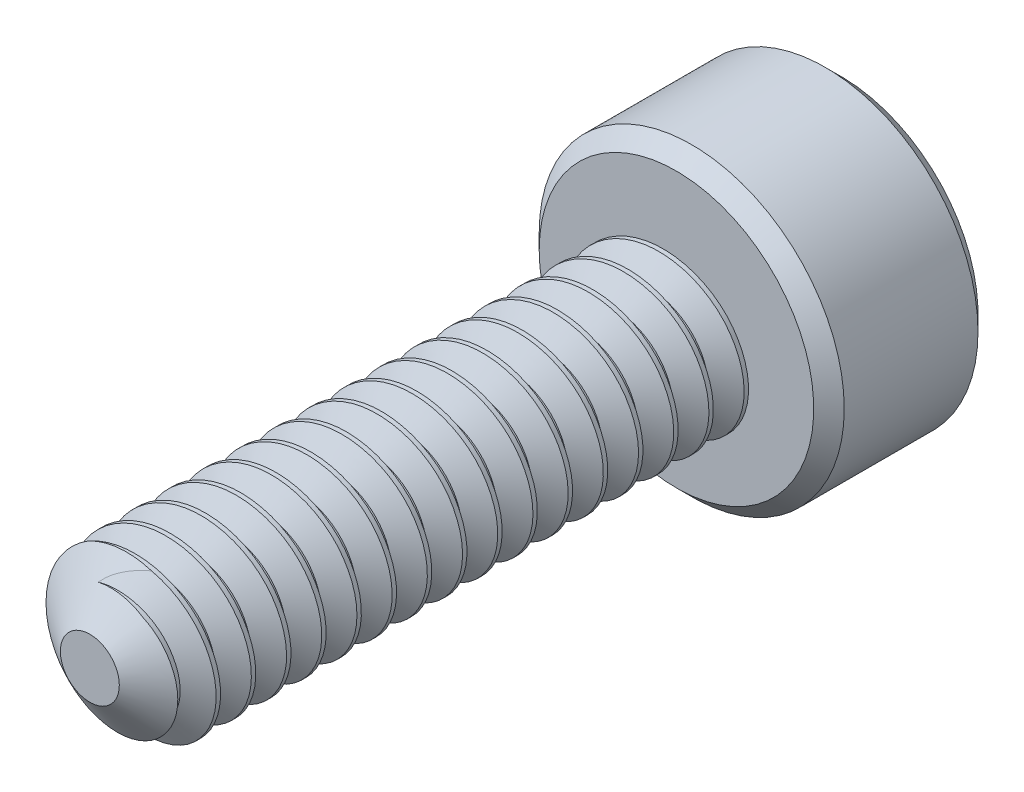
SolidWorks part; units mm, degrees
other "DetailItem1"
ref_plane "Front Plane" through (0, 0, 0) normal (0, 0, 1) x (1, 0, 0)
ref_plane "Top Plane" through (0, 0, 0) normal (0, 1, 0) x (1, 0, 0)
ref_plane "Right Plane" through (0, 0, 0) normal (1, 0, 0) x (0, 0, -1)
sketch "Sketch1" plane through (0, 0, 0) normal (0, 0, 1) x (1, 0, 0)
  circle A0 centre (0, 0) radius 0.7
  dimension "OD" = 1.4
extrude "Extrude1" add sketch "Sketch1" against normal blind 5
sketch "Sketch2" plane through (0, 0, 0) normal (0, 0, 1) x (1, 0, 0)
  circle A0 centre (0, 0) radius 0.7 construction
  circle A1 centre (0, 0) radius 0.7
curve "Helix/Spiral1" pitch 0.3 height 5.3 radius 0.7 centre (0, 0, 0) axis (0, 0, -1) start towards (0, 1, 0) parameters "pitch"=0.3
sketch "Sketch3" plane through (0, 0, 0) normal (1, 0, 0) x (0, 0, -1)
  line L0 (-0.2625, 0.7) -> (-0.15, 0.5051)
  line L1 (-0.15, 0.5051) -> (-0.1125, 0.5051)
  line L2 (-0.1125, 0.5051) -> (0, 0.7)
  line L3 (-0.2625, 0.7) -> (0, 0.7)
  line L4 (-0.1313, 0.7) -> (-0.1313, 0.5051) construction
  line L5 (-0.2063, 0.6026) -> (-0.0563, 0.6026) construction
  line L6 (0, 0.7) -> (0, -0.7) construction
  dimension "D1" = 0.0375
  dimension "D2" = 0.15
  dimension "D3" = 60
sweep "Cut-Sweep1" cut profiles "Sketch3" path "Helix/Spiral1" align with end faces yes
sketch "Sketch4" plane through (0, 0, 0) normal (1, 0, 0) x (0, 0, -1)
  line L0 (0.3143, 0.7) -> (0, 0.2511)
  line L1 (0, 0.2511) -> (0, 0.7)
  line L2 (0.3143, 0.7) -> (0, 0.7)
  line L3 (-0.2625, 0.7) -> (0, 0.7) construction
  line L4 (0, 0) -> (7.0209, 0) construction
  dimension "D1" = 55
  dimension "D2" = 0.254
revolve "Cut-Revolve1" cut sketch "Sketch4" angle 360 about L4
sketch "Sketch6" plane through (0, 0, -5) normal (0, 0, -1) x (-1, 0, 0)
  circle A0 centre (0, 0) radius 1.3
  dimension "head dia" = 2.6
extrude "Extrude2" add sketch "Sketch6" along normal blind 1.4
sketch "Sketch7" plane through (0, 0, -6.4) normal (0, 0, -1) x (-1, 0, 0)
  line L1 (0, 0.7506) -> (-0.65, 0.3753)
  line L2 (-0.65, 0.3753) -> (-0.65, -0.3753)
  line L3 (-0.65, -0.3753) -> (0, -0.7506)
  line L4 (0, -0.7506) -> (0.65, -0.3753)
  line L5 (0.65, -0.3753) -> (0.65, 0.3753)
  line L6 (0.65, 0.3753) -> (0, 0.7506)
  circle A0 centre (0, 0) radius 0.65 construction
  dimension "hex dia" = 1.3
extrude "Cut-Extrude1" cut sketch "Sketch7" against normal blind 0.975
sketch "Sketch8" plane through (0, 0, -6.4) normal (0, 0, -1) x (-1, 0, 0)
  circle A0 centre (0, 0) radius 0.7506
extrude "Cut-Extrude2" cut sketch "Sketch8" against normal through all draft 45
chamfer "Chamfer1" distance 0.13 angle 45 2 edges at (-1.3, 0, -6.4) (-1.3, 0, -5)
sketch "Sketch10" plane through (0, 0, -5) normal (0, 0, 1) x (1, 0, 0)
  circle A1 centre (0, 0) radius 0.7
  circle A2 centre (0, 0) radius 0.7
  dimension "D1" = 0
ref_plane "Plane1" through (0, 0, 0) normal (0, 0, 1) x (1, 0, 0)
extrude "partial thread" [suppressed] add sketch "Sketch10" along normal up to surface (36 mm away) separate body up to plane "Plane1"
chamfer "Chamfer2" [suppressed] distance 0.028 angle 45
combine bodies "Combine1" [suppressed] operation type add bodies to combine 107 108
sketch "Sketch9" plane through (0, 0, 0) normal (1, 0, 0) x (0, 0, -1)
  line L0 (0, 0.7) -> (0, -0.7) construction
  line L1 (0.75, 0.7) -> (0.75, -0.7) construction
  dimension "D1" = 0.75
equation "\"D3@Helix/Spiral1\" = \"screw length@Extrude1\"+\"pitch@Helix/Spiral1\""
equation "\"D1@Sketch3\" = \"pitch@Helix/Spiral1\"*.125"
equation "\"D2@Sketch3\" = \"pitch@Helix/Spiral1\"*.5"
equation "\"D1@Cut-Extrude1\" = \"hex dia@Sketch7\"*.75"
equation "\"D1@Chamfer1\" = \"head dia@Sketch6\"*.05"
equation "\"D1@Sketch9\" = \"pitch@Helix/Spiral1\"*2.5"
equation "\"D1@Chamfer2\"=\"OD@Sketch1\"*.02"
